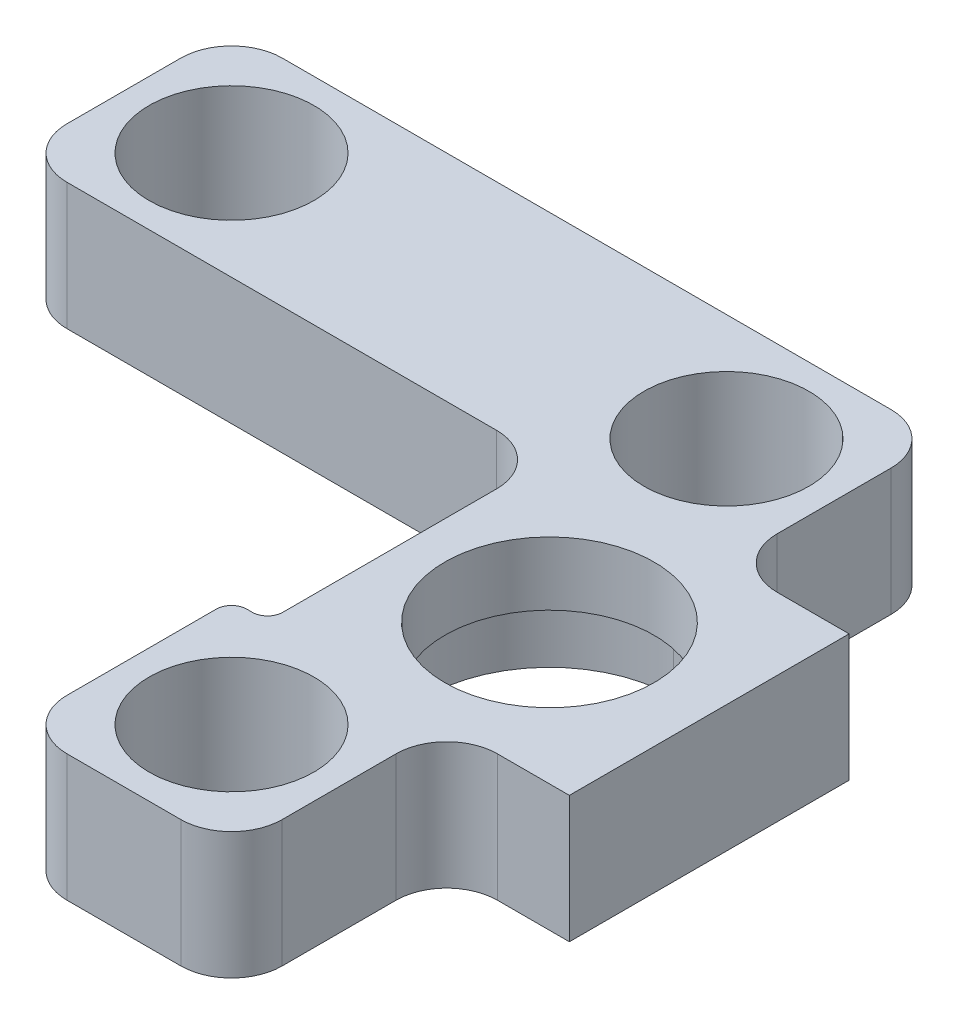
SolidWorks part; units mm, degrees
ref_plane "Front Plane" through (0, 0, 0) normal (0, 0, 1) x (1, 0, 0)
ref_plane "Top Plane" through (0, 0, 0) normal (0, 1, 0) x (1, 0, 0)
ref_plane "Right Plane" through (0, 0, 0) normal (1, 0, 0) x (0, 0, -1)
sketch "Sketch1" plane through (0, 60.9904, 0) normal (0, 1, 0) x (1, 0, 0)
  line L0 (14.6853, 3.6) -> (14.6853, -6) construction
  line L1 (14.6853, -6) -> (9.1853, -6) construction
  line L2 (14.6853, 3.6) -> (9.1853, 3.6) construction
  line L5 (14.7853, 3.7) -> (9.1853, 3.7)
  line L6 (14.7853, 3.7) -> (14.7853, -6.1)
  line L7 (14.7853, -6.1) -> (9.1853, -6.1)
  line L8 (-15.35, 12.8) -> (8.65, 12.8) construction
  line L9 (-17.35, 12.8) -> (10.65, 12.8) construction
  line L10 (-17.35, 12.8) -> (-17.35, 4.3147) construction
  line L11 (-17.35, 4.3147) -> (10.65, 4.3147) construction
  line L12 (10.65, 12.8) -> (10.65, 4.3147) construction
  line L13 (15.4853, -6.7147) -> (3.5853, -6.7147) construction
  line L14 (15.4853, -6.7147) -> (15.4853, 4.3147) construction
  line L15 (15.4853, 4.3147) -> (3.5853, 4.3147) construction
  line L16 (3.5853, -6.7147) -> (3.5853, 4.3147) construction
  line L17 (2.1647, -6.7147) -> (10.65, -6.7147) construction
  line L18 (2.1647, -6.7147) -> (2.1647, -15.2) construction
  line L19 (2.1647, -15.2) -> (10.65, -15.2) construction
  line L20 (10.65, -6.7147) -> (10.65, -15.2) construction
  line L21 (8.65, -15.2) -> (-15.35, -15.2) construction
  line L22 (10.65, 10.8) -> (10.65, -13.2) construction
  line L23 (-17.35, -13.2) -> (-17.35, 10.8) construction
  line L24 (2.1647, -6.7147) -> (10.65, -15.2) construction
  line L25 (4.2853, -1.2) -> (3.5853, -1.2) construction
  line L26 (14.7853, -1.2) -> (15.4853, -1.2) construction
  line L27 (3.5853, 4.3147) -> (-17.35, 4.3147)
  line L28 (-17.35, 4.3147) -> (-17.35, 12.8)
  line L29 (-17.35, 12.8) -> (10.65, 12.8)
  line L30 (10.65, 12.8) -> (10.65, 4.3147)
  line L31 (10.65, 4.3147) -> (15.4853, 4.3147)
  line L32 (15.4853, 4.3147) -> (15.4853, -6.7147)
  line L33 (15.4853, -6.7147) -> (10.65, -6.7147)
  line L34 (10.65, -6.7147) -> (10.65, -15.2)
  line L35 (10.65, -15.2) -> (2.1647, -15.2)
  line L36 (2.1647, -15.2) -> (2.1647, -6.7147)
  line L37 (2.1647, -6.7147) -> (3.5853, -6.7147)
  line L38 (3.5853, -6.7147) -> (3.5853, 4.3147)
  line L39 (6.4689, 3.0211) -> (7.228, 5.1451) construction
  line L40 (6.2845, 2.8024) -> (7.0608, 4.9745) construction
  line L41 (4.3853, 3.6) -> (9.1853, 3.6) construction
  circle A4 centre (6.4074, -10.9574) radius 3.25
  circle A5 centre (-13.1074, 8.5574) radius 3.25
  circle A6 centre (6.4074, 8.5574) radius 3.25
  circle A7 centre (6.4074, -10.9574) radius 3.25 construction
  circle A8 centre (6.4074, 8.5574) radius 3.25 construction
  arc A9 (9.1853, 3.6) -> (9.1853, -6) centre (9.1853, -1.2) ccw construction
  circle A10 centre (-13.1074, 8.5574) radius 3.25 construction
  arc A14 (9.1853, -6) -> (7.0608, 4.9745) centre (9.1853, -0.3071) cw construction
  arc A15 (9.1853, 3.6) -> (6.2845, 2.8024) centre (9.1853, -2.0737) ccw construction
  arc A16 (9.1853, -6.1) -> (7.228, 5.1451) centre (9.1853, -0.3071) cw construction
  arc A17 (9.1853, 3.7) -> (6.4689, 3.0211) centre (9.1853, -2.0737) ccw construction
  arc A18 (9.1853, 3.7) -> (9.1853, -6.1) centre (9.1853, -1.2) ccw
  point P9 (4.2853, -1.2)
  point P10 (0, 0)
  point P11 (8.7979, 3.6)
  point P60 (0, 0)
  point P62 (9.1853, 3.7)
  point P63 (9.1853, 3.7)
  point P64 (9.1568, -6.1)
  point P65 (0, 0)
  point P66 (0, 0)
  arc M43 (9.1853, 3.6) -> (9.1853, -6) centre (9.1853, -1.2) ccw
  line M44 (9.1853, -6) -> (14.6853, -6)
  line M45 (14.6853, -6) -> (14.6853, 3.6)
  line M46 (14.6853, 3.6) -> (9.1853, 3.6)
  circle M47 centre (9.1853, -1.2) radius 4.025
  dimension "D2" = 0.7
  dimension "D1" = 0.1
extrude "Boss-Extrude4" add sketch "Sketch1" against normal blind 2.5
extrude "Boss-Extrude5" add sketch "Sketch1<3>" along normal blind 2.5 contours M46 M43 M44 M45 M47 | L5 A18 L7 L6 M43 M46 M45 M44 | L38 L37 L36 L35 L34 L33 L32 L31 L30 L29 L28 L27 A18 L5 L6 L7 A6 A5 A4 region at (14.7709, 60.9904, 1.2) region at (-6.8824, 60.9904, -4.7462) region at (11.9353, 60.9904, -3.4592)
sketch "Sketch1<3>" plane through (0, 60.9904, 0) normal (0, 1, 0) x (1, 0, 0) same geometry as "Sketch1"
sketch "Sketch3" plane through (0, 63.4904, 0) normal (0, 1, 0) x (1, 0, 0)
  circle A0 centre (9.1853, -1.2) radius 4.125
  circle A1 centre (9.1853, -1.2) radius 4.025 construction
  dimension "D1" = 0.1
extrude "Cut-Extrude1" cut sketch "Sketch3" against normal through all
fillet "Fillet1" radius 0.6 2 edges at (2.1647, 60.9904, 6.7147) (3.5853, 60.9904, 6.7147)
fillet "Fillet2" radius 2 8 edges at (3.5853, 60.9904, -4.3147) (-17.35, 60.9904, -12.8) (-17.35, 60.9904, -4.3147) (10.65, 60.9904, -12.8) (10.65, 60.9904, -4.3147) (10.65, 60.9904, 6.7147) (10.65, 60.9904, 15.2) (2.1647, 60.9904, 15.2)
